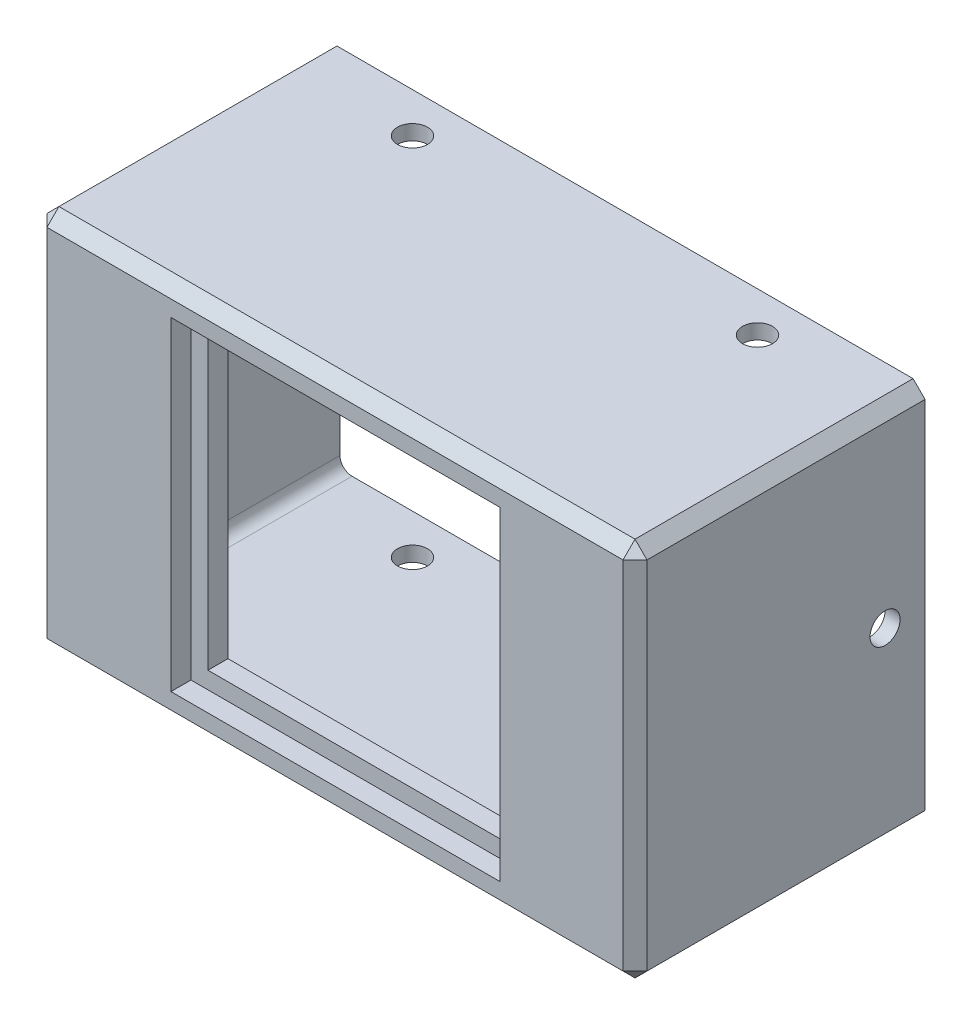
SolidWorks part; units mm, degrees
ref_plane "Plan de face" through (0, 0, 0) normal (0, 0, 1) x (1, 0, 0)
ref_plane "Plan de dessus" through (0, 0, 0) normal (0, 1, 0) x (1, 0, 0)
ref_plane "Plan de droite" through (0, 0, 0) normal (1, 0, 0) x (0, 0, -1)
sketch "Esquisse1" plane through (0, 0, 0) normal (0, 0, 1) x (1, 0, 0)
  line L1 (30, 19) -> (-30, 19)
  line L2 (30, 19) -> (30, -19)
  line L3 (30, -19) -> (-30, -19)
  line L4 (-30, 19) -> (-30, -19)
  line L5 (30, 19) -> (-30, -19) construction
  line L6 (30, -19) -> (-30, 19) construction
  point P0 (0, 0)
  point P6 (0, 0)
  dimension "D1" = 60
  dimension "D2" = 38
extrude "BASE" add sketch "Esquisse1" along normal blind 4
sketch "Esquisse2" plane through (0, 0, 4) normal (0, 0, 1) x (1, 0, 0)
  line L0 (-21.2, 0) -> (26.8, 0) construction
  line L1 (26.8, 16.5) -> (-21.2, 16.5) construction
  line L2 (26.8, 16.5) -> (26.8, -16.5) construction
  line L3 (26.8, -16.5) -> (-21.2, -16.5) construction
  line L4 (-21.2, 16.5) -> (-21.2, -16.5) construction
  line L5 (26.8, 16.5) -> (-21.2, -16.5) construction
  line L6 (26.8, -16.5) -> (-21.2, 16.5) construction
  line L7 (-14.7, 14.5) -> (14.8, 14.5)
  line L8 (-14.7, 14.5) -> (-14.7, -14.5)
  line L9 (-14.7, -14.5) -> (14.8, -14.5)
  line L10 (14.8, 14.5) -> (14.8, -14.5)
  line L11 (30, -19) -> (30, 19) construction
  point P0 (0, 0)
  dimension "D1" = 33
  dimension "D2" = 48
  dimension "D3" = 6.5
  dimension "D4" = 2
  dimension "D5" = 2
  dimension "D6" = 12
  dimension "D7" = 3.2
extrude "Screen" cut sketch "Esquisse2" against normal up to surface (4 mm away) up to face at (0, 0, 0)
sketch "Esquisse5" plane through (0, 0, 0) normal (0, 0, -1) x (-1, 0, 0)
  line L0 (2.2, 0) -> (-2.2, 0) construction
  line L1 (21.2, 16.5) -> (-26.8, 16.5) construction
  line L2 (21.2, 16.5) -> (21.2, -16.5) construction
  line L3 (21.2, -16.5) -> (-26.8, -16.5) construction
  line L4 (-26.8, 16.5) -> (-26.8, -16.5) construction
  line L5 (21.2, 16.5) -> (-26.8, -16.5) construction
  line L6 (21.2, -16.5) -> (-26.8, 16.5) construction
  line L8 (-2.8, 16.5) -> (-2.8, -16.5) construction
  circle A1 centre (-24.3, 14) radius 2.25
  circle A2 centre (-24.3, -14) radius 2.25
  circle A3 centre (18.7, -14) radius 2.25
  circle A4 centre (18.7, 14) radius 2.25
  point P0 (-0.8987, -1.3072)
  dimension "D3" = 4.5
  dimension "D1" = 48
  dimension "D2" = 33
  dimension "D4" = 2.5
  dimension "D5" = 2.5
extrude "Inserts_M3" cut sketch "Esquisse5" against normal blind 3
sketch "Esquisse6" plane through (0, 0, 0) normal (0, 0, -1) x (-1, 0, 0)
  line L0 (-28.5, 17.5) -> (-28.5, -17.5)
  line L1 (-30, 19) -> (30, 19)
  line L2 (-30, 19) -> (-30, -19)
  line L3 (-30, -19) -> (30, -19)
  line L4 (30, 19) -> (30, -19)
  line L5 (-28.5, -17.5) -> (28.5, -17.5)
  line L6 (28.5, 17.5) -> (28.5, -17.5)
  line L7 (-28.5, 17.5) -> (28.5, 17.5)
  dimension "D1" = 1.5
extrude "Walls" add sketch "Esquisse6" along normal blind 25
chamfer "Chanfrein_EXT" distance 1.2 angle 45 8 edges at (0, 19, 4) (30, 19, -10.5) (30, 0, 4) (30, -19, -10.5) (0, -19, 4) (-30, -19, -10.5) (-30, 0, 4) (-30, 19, -10.5)
fillet "Congé1" radius 1.2 8 edges at (0, 17.5, 0) (28.5, 0, 0) (-28.5, 0, 0) (0, -17.5, 0) (-28.5, -17.5, -12.5) (-28.5, 17.5, -12.5) (28.5, -17.5, -12.5) (28.5, 17.5, -12.5)
sketch "Esquisse7" plane through (30, 0, 0) normal (1, 0, 0) x (0, 0, -1)
  line L0 (25, 17.8) -> (25, -17.8) construction
  line L1 (-2.8, 17.8) -> (-2.8, -17.8) construction
  circle A0 centre (21, 0) radius 1.5
  point P7 (-2.8, 0)
  dimension "D1" = 3
  dimension "D2" = 4
extrude "Passage_Vis_Horizontal" cut sketch "Esquisse7" against normal through all
sketch "Esquisse9" plane through (0, 19, 0) normal (0, 1, 0) x (1, 0, 0)
  line L0 (-28.8, 25) -> (28.8, 25) construction
  line L2 (30, 25) -> (30, -2.8) construction
  line L4 (-30, -2.8) -> (-30, 25) construction
  circle A0 centre (-17.25, 21) radius 1.5
  circle A1 centre (17.25, 21) radius 1.5
  point P4 (0, 0)
  point P7 (-17.5315, 21)
  point P8 (0, 0)
  point P11 (-13.006, 21)
  point P12 (-18.9861, 21)
  dimension "D1" = 3
  dimension "D2" = 4
  dimension "D3" = 12.75
  dimension "D4" = 12.75
extrude "Passage_Vis_Vertical" cut sketch "Esquisse9" against normal through all
sketch "Esquisse11" plane through (0, 0, 4) normal (0, 0, 1) x (1, 0, 0)
  line L1 (-16.4, 16.2) -> (16.5, 16.2)
  line L2 (-16.4, 16.2) -> (-16.4, -16.2)
  line L3 (-16.4, -16.2) -> (16.5, -16.2)
  line L4 (16.5, 16.2) -> (16.5, -16.2)
  line L6 (-14.7, 14.5) -> (-14.7, -14.5) construction
  line L7 (-14.7, -14.5) -> (14.8, -14.5) construction
  line L8 (14.8, 14.5) -> (-14.7, 14.5) construction
  line L13 (14.8, -14.5) -> (14.8, 14.5) construction
  dimension "D1" = 1.7
  dimension "D2" = 1.7
  dimension "D3" = 1.7
  dimension "D4" = 1.7
extrude "Emplacement Verre 32.5*32" cut sketch "Esquisse11" against normal blind 2 contours L2 L3 L4 L1
equation "\"D2@Esquisse11\"=\"D1@Esquisse11\""
equation "\"D3@Esquisse11\"=\"D1@Esquisse11\""
equation "\"D4@Esquisse11\"=\"D1@Esquisse11\""
